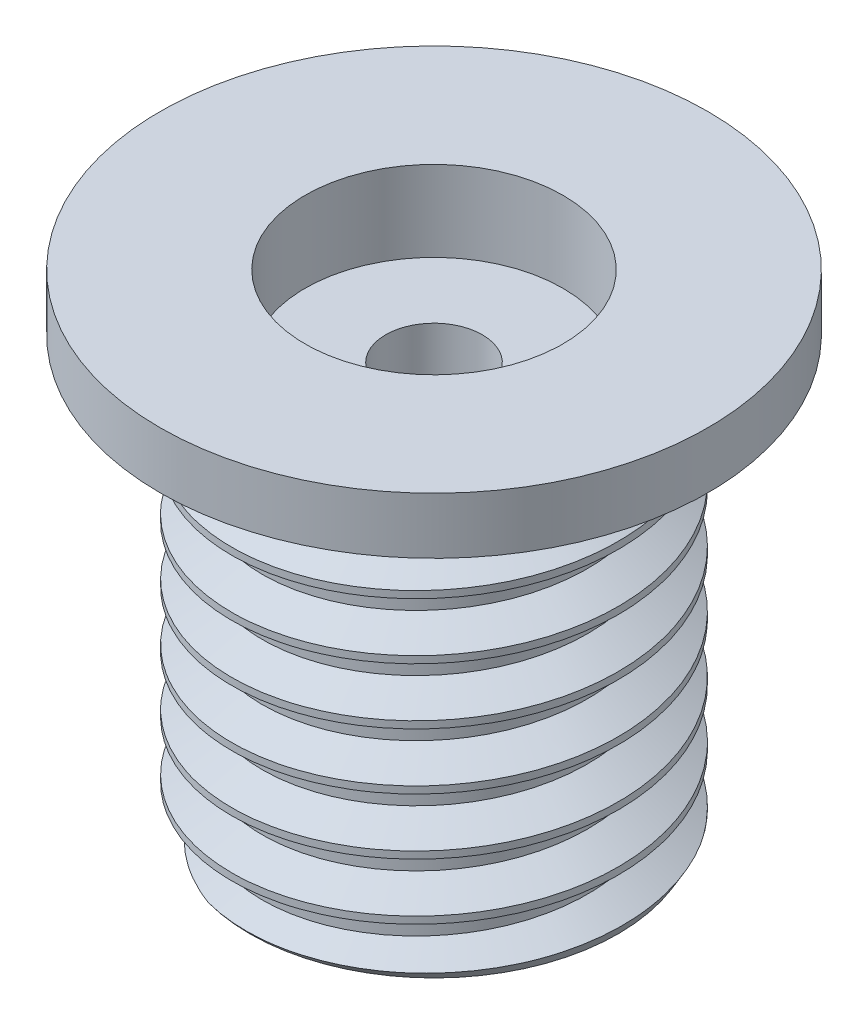
SolidWorks part; units mm, degrees
ref_plane "Front Plane" through (0, 0, 0) normal (0, 0, 1) x (1, 0, 0)
ref_plane "Top Plane" through (0, 0, 0) normal (0, 1, 0) x (1, 0, 0)
ref_plane "Right Plane" through (0, 0, 0) normal (1, 0, 0) x (0, 0, -1)
sketch "Sketch1" plane through (0, 0, 0) normal (1, 0, 0) x (0, 0, -1)
  line L2 (17, 30) -> (17, 26.5)
  line L3 (17, 26.5) -> (12, 26.5)
  line L4 (12, 23.825) -> (12, 0)
  line L6 (0, 0) -> (0, 30) construction
  line L7 (17, 30) -> (8, 30)
  line L8 (8, 30) -> (8, 25)
  line L9 (8, 25) -> (3, 25)
  line L10 (3, 25) -> (3, 5)
  line L11 (3, 5) -> (8, 5)
  line L12 (8, 5) -> (8, 0)
  line L13 (8, 0) -> (12, 0)
  line L14 (12, 26.5) -> (12, 23.825)
  point P6 (3, 26.5732)
  dimension "D1" = 8
  dimension "D2" = 6
  dimension "D3" = 5
  dimension "D4" = 17
  dimension "D5" = 3.5
  dimension "D6" = 30
  dimension "D7" = 12
  dimension "D8" = 5
revolve "Revolve1" add sketch "Sketch1" angle 360 about L6
chamfer "Chamfer1" distance 1 angle 30 1 edges at (0, 0, -12) first distance on face at (0, 26.5, -12)
thread "Thread1" pitch 3.5 method cut profile "Thread Profile1" start angle 0, offset 0, length 26, pitch 3.5, diameter 24
ref_plane "Plane1" through (-12, 26.5, 0) normal (0, 0, 1) x (-1, 0, 0)
sketch "Thread Profile1" plane through (-12, 26.5, 0) normal (0, 0, 1) x (-1, 0, 0)
  line L0 (0, 0) -> (0, 3.5) construction
  line L11 (0, 0) -> (0, 3.0625)
  line L12 (0, 3.0625) -> (-1.8944, 1.9687)
  line L13 (-1.8944, 1.9687) -> (-1.8944, 1.0937)
  line L15 (-1.8944, 1.0937) -> (0, 0)
  line L17 (-1.8944, 1.5312) -> (0, 1.5312) construction
  point P2 (0, 0)
  dimension "Pitch" = 3.5
  dimension "Profile_Angle" = 60
  dimension "Profile_Land" = 0.875
  dimension "Profile_Height" = 1.8944
sketch "Sketch2" plane through (0, 30, 0) normal (0, 1, 0) x (1, 0, 0)
  line L1 (0, 11.547) -> (-10, -5.7735) construction
  line L2 (-10, -5.7735) -> (10, -5.7735) construction
  line L3 (10, -5.7735) -> (0, 11.547) construction
  circle A0 centre (0, 0) radius 5.7735 construction
  circle A1 centre (0, 11.547) radius 1.5
  circle A2 centre (10, -5.7735) radius 1.5
  circle A3 centre (-10, -5.7735) radius 1.5
  dimension "D2" = 3
  dimension "D1" = 20
extrude "Cut-Extrude1" [suppressed] cut sketch "Sketch2" against normal blind 4
